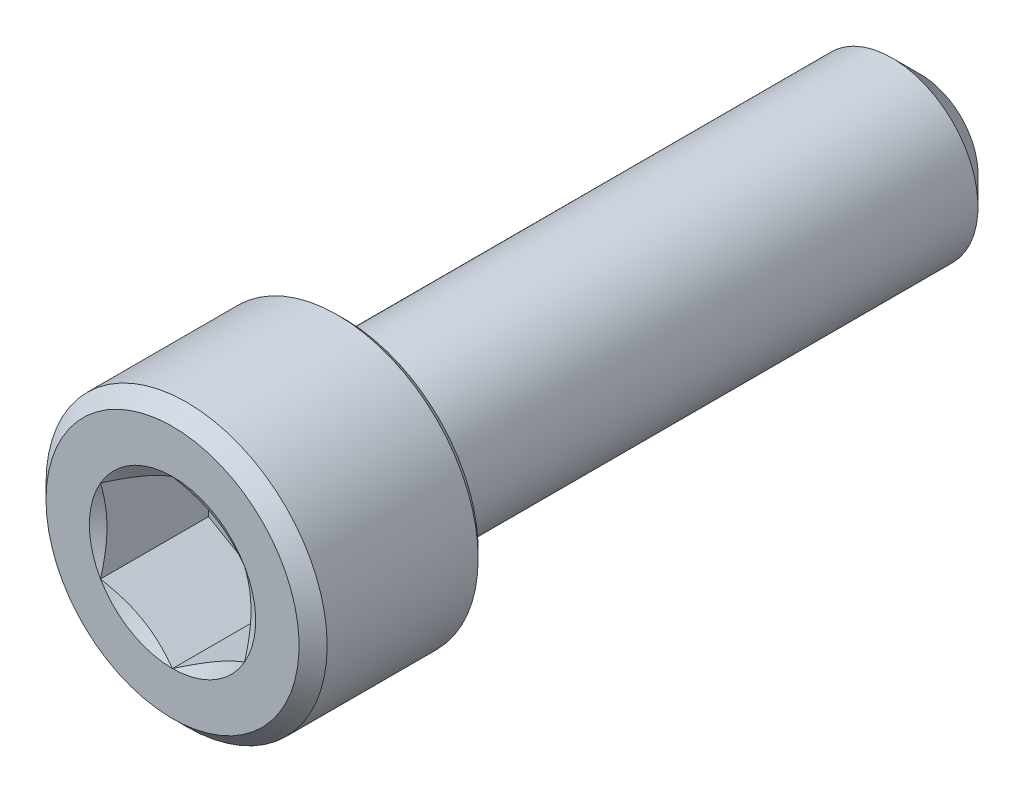
SolidWorks part; units mm, degrees
ref_plane "Front Plane" through (0, 0, 0) normal (0, 0, 1) x (1, 0, 0)
ref_plane "Top Plane" through (0, 0, 0) normal (0, 1, 0) x (1, 0, 0)
ref_plane "Right Plane" through (0, 0, 0) normal (1, 0, 0) x (0, 0, -1)
sketch "Sketch1" plane through (0, 0, 0) normal (1, 0, 0) x (0, 0, -1)
  line L0 (6.1849, 0) -> (-6.1849, 0) construction
  line L1 (-6.1849, 0) -> (-6.1849, 2.3241) construction
  line L2 (-3.3401, 1.4224) -> (-3.3401, 0) construction
  line L3 (5.5499, 0) -> (5.5499, 0.635) construction
  line L4 (-3.3401, 0) -> (-3.3401, -1.4224) construction
  point P6 (-6.1849, 1.1906)
  point P9 (-6.1849, -1.1906)
  point P10 (-3.3401, 0)
  point P13 (3.9624, -1.4224)
  dimension "D1" = 0.635
  dimension "D2" = 2.2225
sketch "Sketch2" plane through (0, 0, 0) normal (1, 0, 0) x (0, 0, -1)
  line L0 (6.1849, 0.9461) -> (5.7086, 1.4224)
  line L1 (-6.1849, 2.3241) -> (-3.3401, 2.3241)
  line L2 (-6.1849, 2.3241) -> (-6.1849, 0)
  line L4 (-3.3401, 2.3241) -> (-3.3401, 1.4224)
  line L5 (-3.3401, 1.4224) -> (5.7086, 1.4224)
  line L8 (6.1849, 0.9461) -> (6.1849, 0)
  line L9 (6.1849, 0) -> (-6.1849, 0) construction
  line L10 (6.1849, 0) -> (-6.1849, 0)
  dimension "D1" = 135
  dimension "D2" = 0.4763
revolve "Revolve1" add sketch "Sketch2" angle 360 about L10
sketch "Sketch4" plane through (0, 0, 6.1849) normal (0, 0, 1) x (1, 0, 0)
  line L1 (0, 1.3748) -> (-1.1906, 0.6874)
  line L2 (-1.1906, 0.6874) -> (-1.1906, -0.6874)
  line L3 (-1.1906, -0.6874) -> (0, -1.3748)
  line L4 (0, -1.3748) -> (1.1906, -0.6874)
  line L5 (1.1906, -0.6874) -> (1.1906, 0.6874)
  line L6 (1.1906, 0.6874) -> (0, 1.3748)
  circle A0 centre (0, 0) radius 1.1906 construction
  circle A1 centre (0, 0) radius 2.3241 construction
  circle A2 centre (0, 0) radius 2.3241 construction
  dimension "D1" = 2.3813
extrude "Cut-Extrude1" cut sketch "Sketch4" against normal blind 1.7859
sketch "Sketch5" plane through (0, 0, 6.1849) normal (0, 0, 1) x (1, 0, 0)
  circle A0 centre (0, 0) radius 1.3748
extrude "Cut-Extrude2" cut sketch "Sketch5" against normal blind 10 draft 60
chamfer "Chamfer1" distance 0.2324 angle 45 1 edges at (-2.3241, 0, 6.1849)
chamfer "Chamfer2" distance 0.1162 angle 45 1 edges at (-2.3241, 0, 3.3401)
sketch "Sketch3" [suppressed] plane through (0, 0, -6.1849) normal (0, 0, -1) x (-1, 0, 0)
  circle A0 centre (0, 0) radius 1.4224 construction
  circle A1 centre (0, 0) radius 1.4224
ref_axis "Center Axis1" through (0, 0, -5.7312) along (0, 0, 1)
ref_plane "Contact Plane1" through (0, 0, -6.1849) normal (0, 0, 1) x (1, 0, 0)
ref_plane "Contact Plane2" through (0, 0, 3.3401) normal (0, 0, 1) x (1, 0, 0)
split "Split1" [suppressed] bodies to split 106
curve "Helix/Spiral1" [suppressed] pitch 0.635 height 10.16 turns 16
sketch "Sketch7" [suppressed] plane through (0, 0, 0) normal (1, 0, 0) x (0, 0, -1)
  line L0 (6.1452, 1.4911) -> (6.4627, 0.9412) construction
  line L1 (6.4627, 0.9412) -> (6.7802, 1.4911) construction
  line L2 (6.7802, 1.4911) -> (6.1452, 1.4911) construction
  line L3 (6.1849, 1.4224) -> (6.7405, 1.4224)
  line L4 (6.4627, 1.4911) -> (6.4627, 1.4224) construction
  line L5 (6.4627, 1.4224) -> (6.4627, 1.01) construction
  line L6 (6.4627, 1.01) -> (6.4627, 0.9412) construction
  line L7 (6.423, 1.01) -> (6.5024, 1.01)
  line L8 (6.1651, 1.4568) -> (6.7604, 1.4568) construction
  line L9 (6.5024, 1.01) -> (6.7405, 1.4224)
  line L10 (6.423, 1.01) -> (6.1849, 1.4224)
  point P0 (6.4627, 1.4568)
  dimension "D1" = 0.635
  dimension "D2" = 0.0794
sweep "Cut-Sweep1" [suppressed] cut profiles "Sketch7" path "Helix/Spiral1"
sketch "Sketch11" [suppressed] plane through (0, 0, 3.3401) normal (0, 0, -1) x (-1, 0, 0)
  circle A0 centre (0, 0) radius 1.4224
extrude "Boss-Extrude4" [suppressed] add sketch "Sketch11" along normal through all draft 45
sketch "Sketch9" [suppressed] plane through (0, 0, 3.3401) normal (0, 0, -1) x (-1, 0, 0)
  line L0 (0, 0) -> (0, 2.3241) construction
  line L1 (0, 2.2079) -> (-0.2436, 2.4403)
  line L2 (-0.2436, 2.4403) -> (0.2436, 2.4403)
  line L3 (0.2436, 2.4403) -> (0, 2.2079)
  line L4 (-0.1218, 2.3241) -> (0, 0) construction
  line L5 (0, 0) -> (0.1218, 2.3241) construction
  circle A0 centre (0, 0) radius 2.3241 construction
  circle A1 centre (0, 0) radius 2.2079 construction
  dimension "D1" = 0.2324
  dimension "D2" = 6
extrude "Cut-Extrude3" [suppressed] cut sketch "Sketch9" against normal up to next
pattern_circular "CirPattern1" [suppressed] count 60 over 360 of bodies 112
equation "\"D1@Sketch1\"=\"Pitch@Sketch1\""
equation "\"D2@Sketch2\"=\"D1@Sketch1\"*.75"
equation "\"D4@Helix/Spiral1\"=\"Pitch@Sketch1\""
equation "\"D3@Helix/Spiral1\"=\"Length@Sketch1\"+\"Pitch@Sketch1\""
equation "\"D1@Sketch4\" = \"Drive Size@Sketch1\""
equation "\"D1@Cut-Extrude1\"=\"D1@Sketch4\"*.75"
equation "\"D19\"= \"D1@Sketch4\" * .75"
equation "\"D1@Chamfer1\" = \"Head Diameter@Sketch1\" * .05"
equation "\"D1@Chamfer2\"=\"D1@Chamfer1\"/2"
equation "\"D2@Sketch7\"=\"D1@Sketch7\"/8"
equation "\"D1@Sketch7\"=\"D4@Helix/Spiral1\""
equation "\"D2@Sketch1\"=\"Pitch@Sketch1\"*3.5"
equation "\"D1@Sketch9\"=\"D1@Chamfer1\""
equation "\"D1@CirPattern1\"=\"D3@CirPattern1\"/\"D2@Sketch9\""
